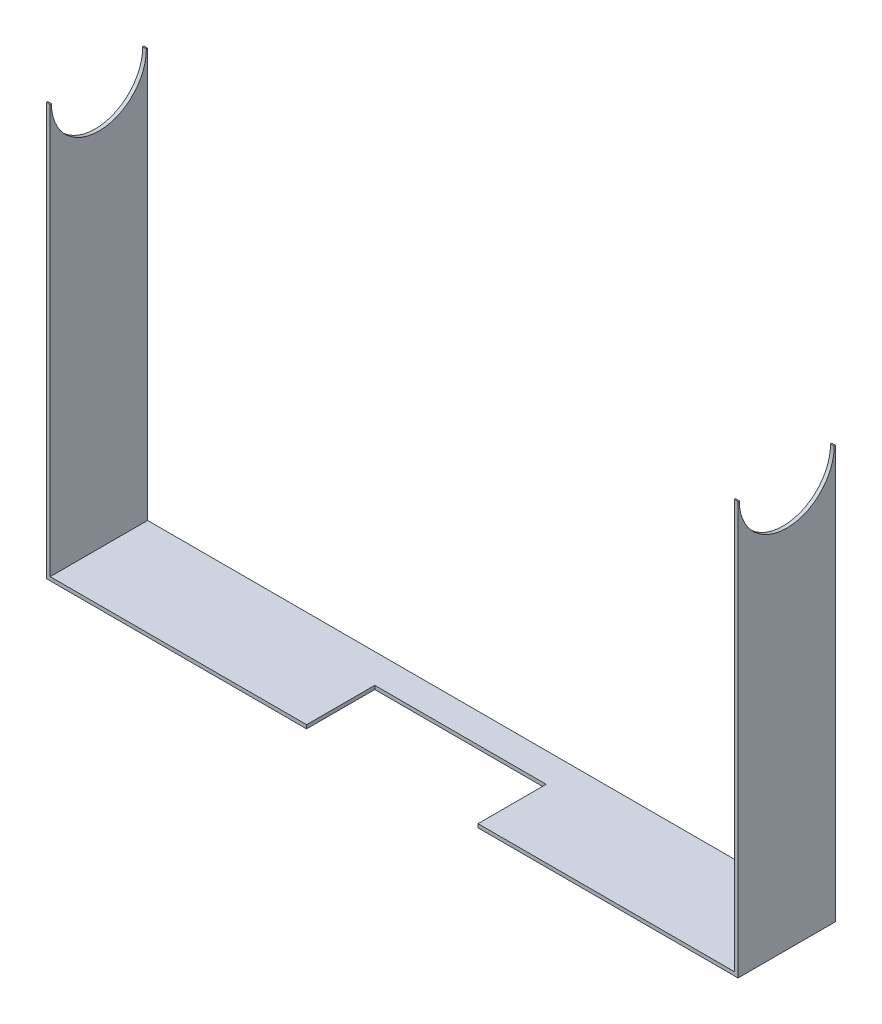
SolidWorks part; units mm, degrees
ref_plane "前视基准面" through (0, 0, 0) normal (0, 0, 1) x (1, 0, 0)
ref_plane "上视基准面" through (0, 0, 0) normal (0, 1, 0) x (1, 0, 0)
ref_plane "右视基准面" through (0, 0, 0) normal (1, 0, 0) x (0, 0, -1)
sketch "草图1" plane through (0, 0, 0) normal (0, 0, 1) x (1, 0, 0)
  line L0 (-52.9873, 27.7486) -> (-52.9873, -141.7514)
  line L1 (-52.9873, -141.7514) -> (231.0127, -141.7514)
  line L2 (231.0127, -141.7514) -> (231.0127, 27.7486)
  line L3 (231.0127, 27.7486) -> (229.5127, 27.7486)
  line L4 (229.5127, 27.7486) -> (229.5127, -140.2514)
  line L5 (229.5127, -140.2514) -> (-51.4873, -140.2514)
  line L6 (-51.4873, -140.2514) -> (-51.4873, 27.7486)
  line L7 (-51.4873, 27.7486) -> (-52.9873, 27.7486)
extrude "凸台-拉伸1" add sketch "草图1" along normal blind 40
sketch "草图2" plane through (-51.4873, 0, 0) normal (1, 0, 0) x (0, 0, -1)
  line L0 (-40, 27.7486) -> (0, 27.7486) construction
  circle A0 centre (-20, 27.7486) radius 19.5
extrude "切除-拉伸1" cut sketch "草图2" against normal blind 39 and the other way blind 368
sketch "草图4" plane through (0, -140.2514, 0) normal (0, 1, 0) x (1, 0, 0)
  line L0 (89.0127, 0) -> (89.0127, -65.2755) construction
  line L1 (229.5127, 0) -> (-51.4873, 0) construction
  line L2 (89.0127, -40) -> (53.8127, -40)
  line L3 (229.5127, -40) -> (-51.4873, -40) construction
  line L4 (53.8127, -40) -> (53.8127, -12)
  line L5 (53.8127, -12) -> (89.0127, -12)
  line L6 (89.0127, -12) -> (124.2127, -12)
  line L7 (124.2127, -12) -> (124.2127, -40)
  line L8 (124.2127, -40) -> (89.0127, -40)
extrude "切除-拉伸2" cut sketch "草图4" against normal blind 39
